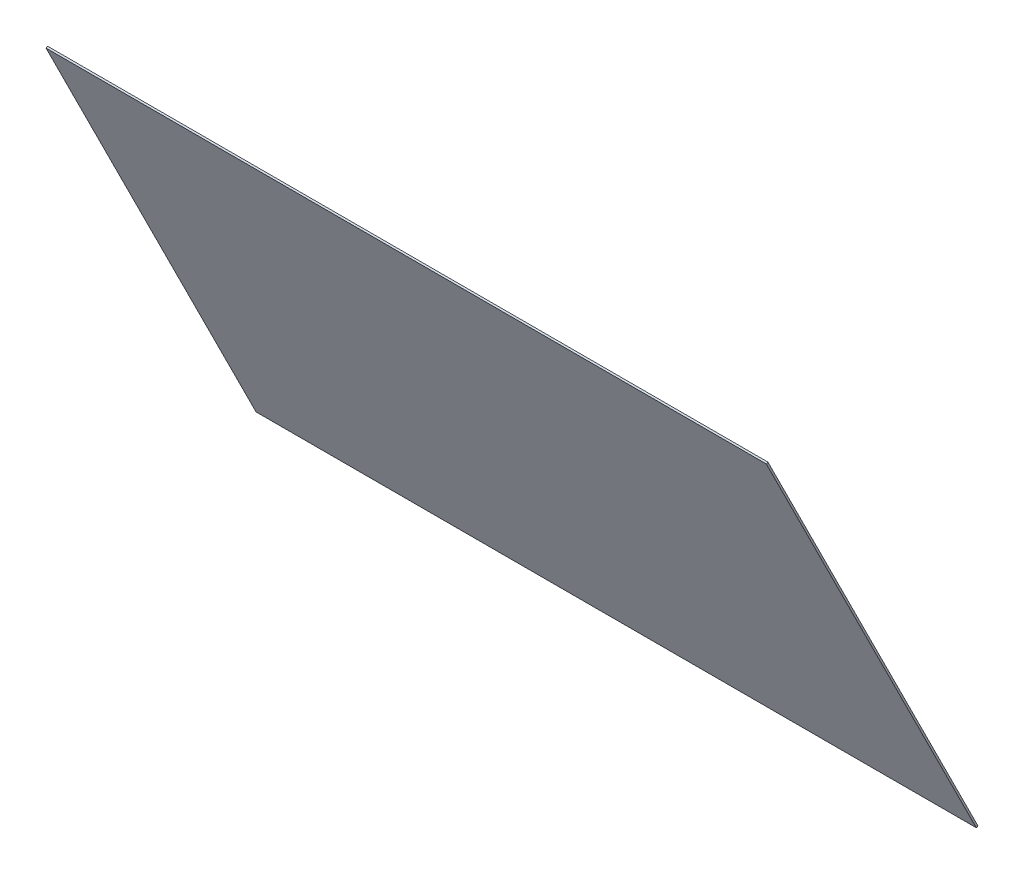
SolidWorks part; units mm, degrees
material "AISI 304"
ref_plane "Front Plane" through (0, 0, 0) normal (0, 0, 1) x (1, 0, 0)
ref_plane "Top Plane" through (0, 0, 0) normal (0, 1, 0) x (1, 0, 0)
ref_plane "Right Plane" through (0, 0, 0) normal (1, 0, 0) x (0, 0, -1)
sketch "Sketch1" plane through (0, 0, 0) normal (1, 0, 0) x (0, 0, -1)
  line L0 (0, 0) -> (350, -700)
  line L1 (0, 0) -> (550, 0) construction
  line L2 (350, -700) -> (550, -700) construction
  line L3 (550, -700) -> (550, 0) construction
  dimension "D1" = 550
  dimension "D2" = 200
  dimension "D3" = 700
base flange "Base-Flange1" sketch "Sketch1" end condition mid plane depth 1200 reverse direction yes thickness 3 reverse thickness direction no bend radius 0.7366
sketch "Bend-Lines1" [suppressed] plane through (0, 0, 0) normal (0, 1, 0) x (1, 0, 0)
sketch "Bounding-Box1" [suppressed] plane through (0, 0, 0) normal (0, 1, 0) x (1, 0, 0)
sheet metal parameters "Sheet-Metal1" thickness 3 parameters "D1"=0.7366
flat pattern "Flat-Pattern1" [suppressed]
sketch "Bend-Lines2" plane through (0, 0, 0) normal (0, 1, 0) x (1, 0, 0)
sketch3d "Bounding-Box2" [suppressed]
  line L0 (-1200, -782.6238, 0) -> (0, -782.6238, 0) construction
  line L1 (-1200, 0, 0) -> (0, 0, 0) construction
  line L2 (-1200, -782.6238, 0) -> (-1200, 0, 0) construction
  line L3 (0, -782.6238, 0) -> (0, 0, 0) construction
